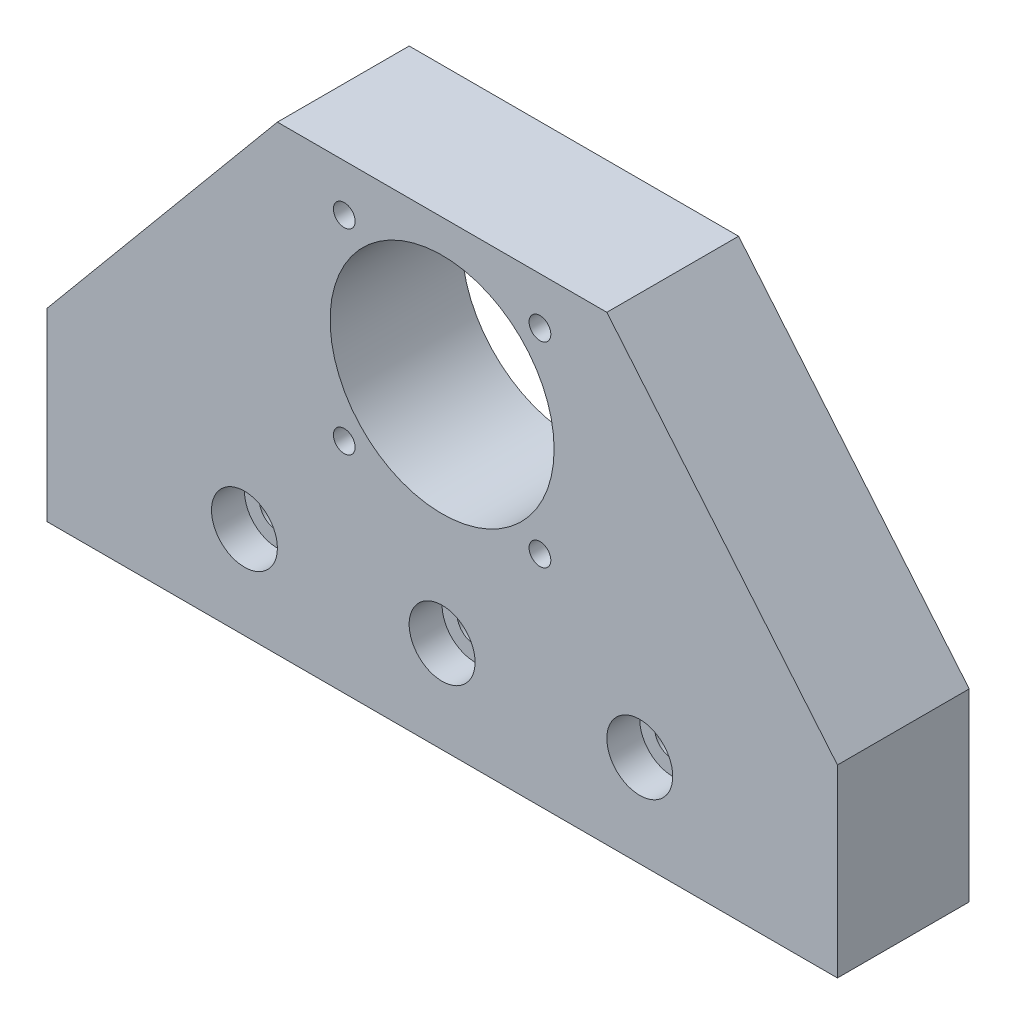
SolidWorks part; units mm, degrees
ref_plane "Front Plane" through (0, 0, 0) normal (0, 0, 1) x (1, 0, 0)
ref_plane "Top Plane" through (0, 0, 0) normal (0, 1, 0) x (1, 0, 0)
ref_plane "Right Plane" through (0, 0, 0) normal (1, 0, 0) x (0, 0, -1)
sketch "Sketch1" plane through (0, 0, 0) normal (0, 0, 1) x (1, 0, 0)
  line L0 (60, 0) -> (-60, 0)
  line L1 (-60, 0) -> (-60, 28)
  line L2 (-60, 28) -> (-25, 70)
  line L3 (-25, 70) -> (25, 70)
  line L4 (0, 0) -> (0, 70) construction
  line L5 (60, 28) -> (25, 70)
  line L6 (60, 0) -> (60, 28)
  dimension "D1" = 120
  dimension "D2" = 28
  dimension "D3" = 50
  dimension "D4" = 70
extrude "Boss-Extrude1" add sketch "Sketch1" along normal blind 20
sketch "Sketch2" plane through (0, 0, 20) normal (0, 0, 1) x (1, 0, 0)
  line L0 (0, 0) -> (0, 70) construction
  line L1 (-60, 0) -> (60, 0) construction
  line L2 (25, 70) -> (-25, 70) construction
  line L3 (-60, 14) -> (60, 14) construction
  line L4 (-60, 28) -> (-60, 0) construction
  line L5 (60, 0) -> (60, 28) construction
  point P12 (0, 14)
  point P13 (-30, 14)
  point P14 (30, 14)
  point P15 (0, 48)
  dimension "D1" = 30
hole_wizard "CBORE for M5 SHCS1" positions "3DSketch1" profile "Sketch3" counterbore size "M5" standard "ANSI Metric" end condition through all
sketch3d "3DSketch1"
  point P0 (-30, 14, 20)
  point P3 (0, 14, 20)
  point P6 (30, 14, 20)
sketch "Sketch3" plane through (-30, 14, 20) normal (1, 0, 0) x (0, -1, 0)
  line L0 (0, 0) -> (0, 20)
  line L1 (0, 20) -> (2.75, 20)
  line L3 (2.75, 20) -> (2.75, 5)
  line L4 (2.75, 5) -> (5, 5)
  line L5 (5, 5) -> (5, 0)
  line L7 (5, 0) -> (0, 0)
  line L11 (0, -6.35) -> (0, 107.95) construction
  dimension "Thru Hole Dia." = 5.5
  dimension "Thru Hole Depth" = 20
  dimension "C'Bore Dia." = 10
  dimension "C'Bore Depth" = 5
sketch "Sketch4" plane through (0, 0, 20) normal (0, 0, 1) x (1, 0, 0)
  circle A0 centre (0, 48) radius 17
  dimension "D1" = 34
extrude "Cut-Extrude1" cut sketch "Sketch4" against normal through all
sketch "Sketch5" plane through (0, 0, 20) normal (0, 0, 1) x (1, 0, 0)
  point P0 (14.8492, 33.1508)
  point P1 (-14.8492, 33.1508)
  point P2 (-14.8492, 62.8492)
  point P3 (14.8492, 62.8492)
hole_wizard "M4 Tapped Hole1" positions "3DSketch3" profile "Sketch7" tap size "M4" standard "ISO" end condition through all
sketch3d "3DSketch3"
  point P0 (-14.8492, 62.8492, 20)
  point P3 (14.8492, 62.8492, 20)
  point P6 (14.8492, 33.1508, 20)
  point P9 (-14.8492, 33.1508, 20)
sketch "Sketch7" plane through (-14.8492, 62.8492, 20) normal (1, 0, 0) x (0, -1, 0)
  line L0 (0, 0) -> (0, 20)
  line L1 (0, 20) -> (1.65, 20)
  line L2 (1.65, 20) -> (1.65, 0)
  line L5 (1.65, 0) -> (0, 0)
  line L11 (0, -6.35) -> (0, 107.95) construction
  dimension "Thread Major Dia." = 3.3
  dimension "Thru Tap Drill Depth" = 20
sketch "Sketch8" plane through (0, 0, 0) normal (0, -1, 0) x (1, 0, 0)
  line L0 (-20.1, 18.72) -> (-20.1, 0) construction
  line L1 (-60, 0) -> (60, 0) construction
  line L2 (20.1, 18.72) -> (20.1, 0) construction
  line L3 (-60, 10) -> (60, 10) construction
  line L4 (-60, 20) -> (-60, 0) construction
  line L5 (60, 20) -> (60, 0) construction
  point P12 (-20.1, 10)
  point P13 (20.1, 10)
hole_wizard "M4 Tapped Hole2" positions "Sketch10" profile "Sketch11" tap size "M4" standard "ISO"
sketch "Sketch10" plane through (0, 0, 0) normal (0, -1, 0) x (-1, 0, 0)
  point P0 (20.1, -10)
  point P3 (-20.1, -10)
sketch "Sketch11" plane through (-20.1, 0, 10) normal (1, 0, 0) x (0, 0, -1)
  line L0 (0, 0) -> (0, 15.9914)
  line L1 (0, 15.9914) -> (1.65, 15)
  line L2 (1.65, 15) -> (1.65, 0)
  line L5 (1.65, 0) -> (0, 0)
  line L10 (0, 15.9914) -> (-1.65, 15) construction
  line L11 (0, -6.35) -> (0, 107.95) construction
  dimension "Tap Drill Dia." = 3.3
  dimension "Tap Drill Depth" = 15
  dimension "Drill Angle" = 118
